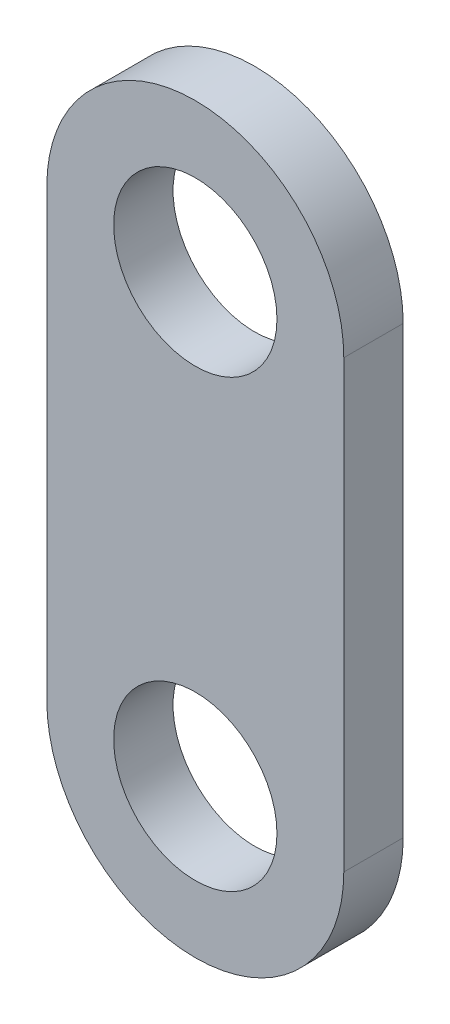
SolidWorks part; units mm, degrees
material "ABS"
ref_plane "Front Plane" through (0, 0, 0) normal (0, 0, 1) x (1, 0, 0)
ref_plane "Top Plane" through (0, 0, 0) normal (0, 1, 0) x (1, 0, 0)
ref_plane "Right Plane" through (0, 0, 0) normal (1, 0, 0) x (0, 0, -1)
ref_axis "X" through (-88.99, 0, 0) along (1, 0, 0)
ref_axis "Y" through (0, 55, 0) along (0, -1, 0)
ref_axis "Z" through (0, 0, -88.99) along (0, 0, 1)
sketch "Sketch1" plane through (0, 0, 0) normal (0, 0, 1) x (1, 0, 0)
  line L0 (0, 7.5) -> (0, -7.5) construction
  line L2 (5, 7.5) -> (5, -7.5)
  line L3 (-5, 7.5) -> (-5, -7.5)
  arc A0 (5, 7.5) -> (-5, 7.5) centre (0, 7.5) ccw
  arc A1 (-5, -7.5) -> (5, -7.5) centre (0, -7.5) ccw
  circle A2 centre (0, 7.5) radius 2.5 construction
  circle A3 centre (0, -7.5) radius 2.5 construction
  point P5 (0, 0)
  dimension "D2" = 5
  dimension "D3" = 2.5
  dimension "D1" = 15
extrude "Boss-Extrude1" add sketch "Sketch1" along normal blind 2
sketch "Sketch4" plane through (0, 0, 2) normal (0, 0, 1) x (1, 0, 0)
  point P0 (0, 7.5)
  point P3 (0, -7.5)
hole_wizard "M5 Clearance Hole1" positions "Sketch4" profile "Sketch3" hole size "M5" standard "ANSI Metric" end condition through all
sketch "Sketch3" plane through (0, 7.5, 2) normal (1, 0, 0) x (0, -1, 0)
  line L0 (0, 0) -> (0, 2)
  line L1 (0, 2) -> (2.75, 2)
  line L2 (2.75, 2) -> (2.75, 0)
  line L5 (2.75, 0) -> (0, 0)
  line L11 (0, -6.35) -> (0, 107.95) construction
  dimension "Thru Hole Dia." = 5.5
  dimension "Thru Hole Depth" = 2
